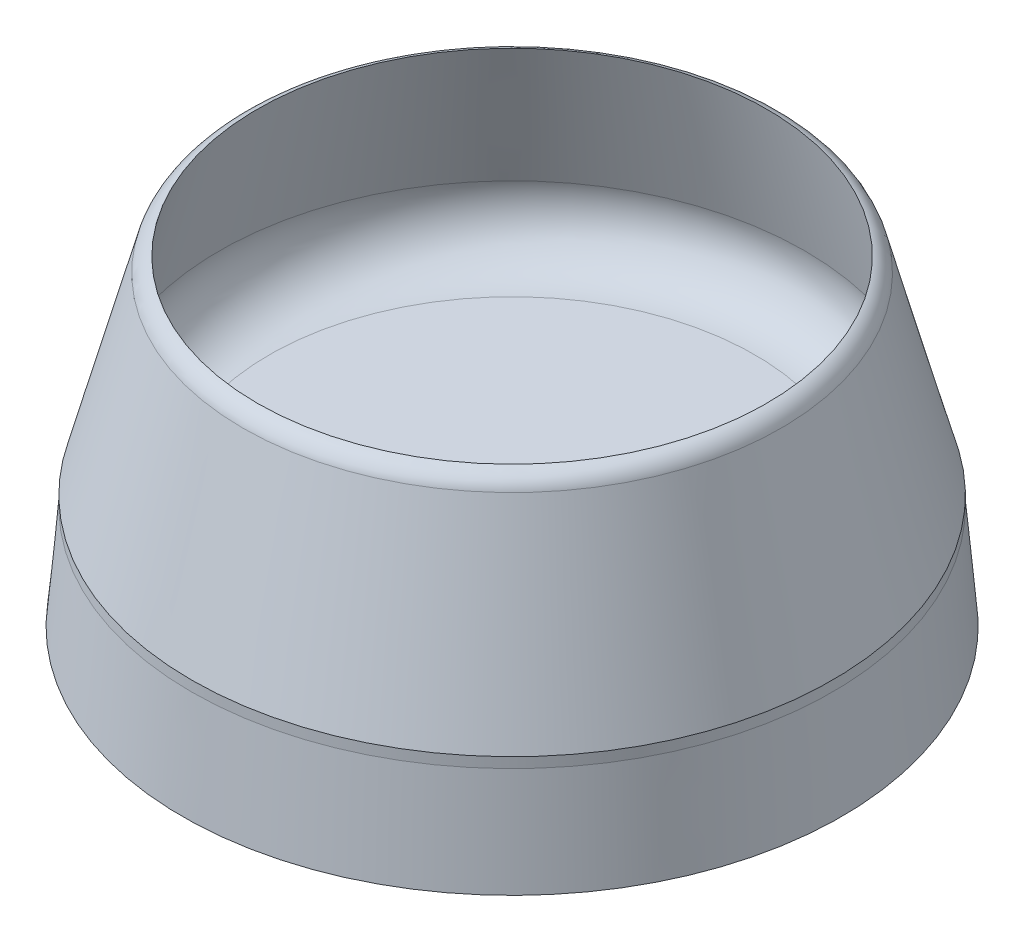
SolidWorks part; units mm, degrees
material "PE High Density"
ref_plane "Front Plane" through (0, 0, 0) normal (0, 0, 1) x (1, 0, 0)
ref_plane "Top Plane" through (0, 0, 0) normal (0, 1, 0) x (1, 0, 0)
ref_plane "Right Plane" through (0, 0, 0) normal (1, 0, 0) x (0, 0, -1)
sketch "Sketch1" plane through (0, 0, 0) normal (0, 1, 0) x (1, 0, 0)
  circle A0 centre (0, 0) radius 39.37
  dimension "D1" = 78.74
extrude "Boss-Extrude1" add sketch "Sketch1" along normal mid plane 1.27
sketch "Sketch4" plane through (0, 0.635, 0) normal (0, 1, 0) x (1, 0, 0)
  circle A0 centre (0, 0) radius 39.37
  dimension "D1" = 78.74
extrude "Boss-Extrude2" add sketch "Sketch4" along normal blind 25.4 draft 15
sketch "Sketch5" plane through (0, 26.035, 0) normal (0, 1, 0) x (1, 0, 0)
  circle A0 centre (0, 0) radius 32.5641
  circle A1 centre (0, 0) radius 31.2941
  circle A2 centre (0, 0) radius 32.5641
  circle A3 centre (0, 0) radius 31.2941
  dimension "D1" = 65.1282
  dimension "D2" = 62.5882
extrude "Cut-Extrude2" cut sketch "Sketch5" against normal blind 25.4 draft 15 contours A1 region at (0, 26.035, 0) draft outward yes
sketch "Sketch6" plane through (0, -0.635, 0) normal (0, -1, 0) x (1, 0, 0)
  circle A0 centre (0, 0) radius 39.37
extrude "Boss-Extrude3" add sketch "Sketch6" along normal blind 12.7 draft 5 draft outward yes
sketch "Sketch7" plane through (0, -13.335, 0) normal (0, -1, 0) x (1, 0, 0)
  circle A0 centre (0, 0) radius 40.4811
  dimension "D1" = 80.9622
sketch "Sketch8" plane through (0, -13.335, 0) normal (0, -1, 0) x (1, 0, 0)
  circle A0 centre (0, 0) radius 39.2111
  dimension "D1" = 78.4222
extrude "Cut-Extrude3" cut sketch "Sketch8" against normal blind 12.7 draft 5
sketch "Sketch9" plane through (0, -0.635, 0) normal (0, -1, 0) x (1, 0, 0)
  line L0 (0, 38.1) -> (0, -38.1) construction
  line L1 (-38.1, 0) -> (38.1, 0) construction
  circle A0 centre (0, 0) radius 38.1 construction
  circle A1 centre (0, 0) radius 19.05 construction
  circle A2 centre (0, 0) radius 9.525 construction
  circle A3 centre (0, 9.525) radius 1.5875
  circle A4 centre (0, -9.525) radius 1.5875
  dimension "D1" = 3.175
  dimension "D2" = 3.175
extrude "Boss-Extrude4" add sketch "Sketch9" along normal blind 19.05
sketch "Sketch11" plane through (0, -19.685, 0) normal (0, -1, 0) x (1, 0, 0)
  circle A0 centre (0, -9.525) radius 1.5875
ref_plane "Plane1" through (0, -19.685, 0) normal (0, -1, 0) x (-1, 0, 0)
sketch "Sketch12" plane through (0, -19.685, 0) normal (0, -1, 0) x (-1, 0, 0)
  line L0 (0, 9.525) -> (0, -11.1125) construction
  line L1 (0, 0) -> (18.9344, 0) construction
  circle A0 centre (0, -9.525) radius 1.5875 construction
  circle A1 centre (0, 9.525) radius 1.5875
revolve "Revolve1" add sketch "Sketch12" angle 180 about L1
fillet "Fillet1" radius 6.35 1 edges at (0, 0.635, 38.1)
fillet "Fillet3" radius 2.54 1 edges at (0, 26.035, 32.5641)
fillet "Fillet4" radius 6.35 1 edges at (0, -0.635, -38.1)
fillet "Fillet5" radius 2.54 1 edges at (0, -13.335, -39.2111)
